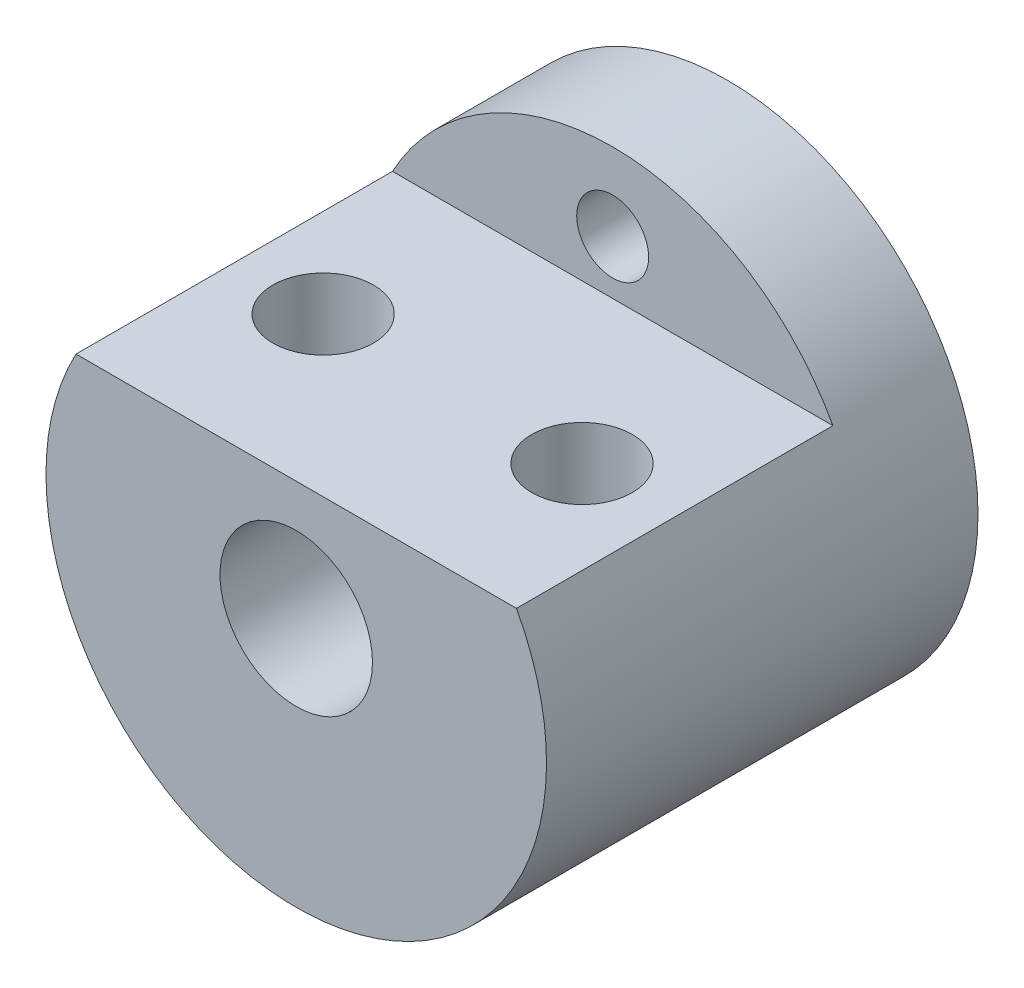
SolidWorks part; units mm, degrees
ref_plane "Front Plane" through (0, 0, 0) normal (0, 0, 1) x (1, 0, 0)
ref_plane "Top Plane" through (0, 0, 0) normal (0, 1, 0) x (1, 0, 0)
ref_plane "Right Plane" through (0, 0, 0) normal (1, 0, 0) x (0, 0, -1)
sketch "Sketch1" plane through (0, 0, 0) normal (0, 0, 1) x (1, 0, 0)
  circle A0 centre (0, 0) radius 8.7
  dimension "D1" = 17.4
extrude "Boss-Extrude1" add sketch "Sketch1" along normal blind 15 contours A0
sketch "Sketch2" plane through (0, 0, 15) normal (0, 0, 1) x (1, 0, 0)
  line L1 (-7.6555, 8.7) -> (9.3445, 8.7)
  line L2 (-7.6555, 8.7) -> (-7.6555, 4.1331)
  line L3 (-7.6555, 4.1331) -> (9.3445, 4.1331)
  line L4 (9.3445, 8.7) -> (9.3445, 4.1331)
  circle A0 centre (0, 0) radius 8.7 construction
  dimension "D1" = 17
sketch "Sketch4" plane through (0, 0, 0) normal (0, 0, -1) x (-1, 0, 0)
  circle A0 centre (0, 6) radius 1.25
  circle A1 centre (6, 0) radius 1.25
  circle A2 centre (0, -6) radius 1.25
  circle A3 centre (-6, 0) radius 1.25
  dimension "D1" = 2.5
  dimension "D2" = 6
  dimension "D3" = 6
  dimension "D4" = 6
  dimension "D5" = 6
sketch "Sketch5" plane through (0, 0, 0) normal (0, 0, -1) x (-1, 0, 0)
  circle A0 centre (0, 0) radius 1.75
  dimension "D1" = 3.5
extrude "Cut-Extrude1" cut sketch "Sketch5" against normal through all
extrude "Cut-Extrude2" cut sketch "Sketch4" against normal blind 7
sketch "Sketch6" plane through (0, 0, 15) normal (0, 0, 1) x (1, 0, 0)
  circle A0 centre (0, 0) radius 2.65
  dimension "D1" = 5.3
extrude "Cut-Extrude3" cut sketch "Sketch6" against normal blind 6.4
extrude "Cut-Extrude4" cut sketch "Sketch2" against normal blind 11 contours L1 L4 L3 L2
fillet "Fillet1" radius 0.3 1 edges at (1.75, 0, 8.6)
sketch "Sketch8" plane through (0, 4.1331, 0) normal (0, 1, 0) x (1, 0, 0)
  line L0 (-7.6555, -4) -> (-7.6555, -15) construction
  line L1 (7.6555, -4) -> (7.6555, -15) construction
  circle A2 centre (-4.5645, -9.5) radius 1.75
  circle A3 centre (4.4355, -9.5) radius 1.75
  dimension "D1" = 3.5
  dimension "D2" = 3.091
  dimension "D3" = 3.2201
extrude "Cut-Extrude6" cut sketch "Sketch8" against normal through all and the other way through all
